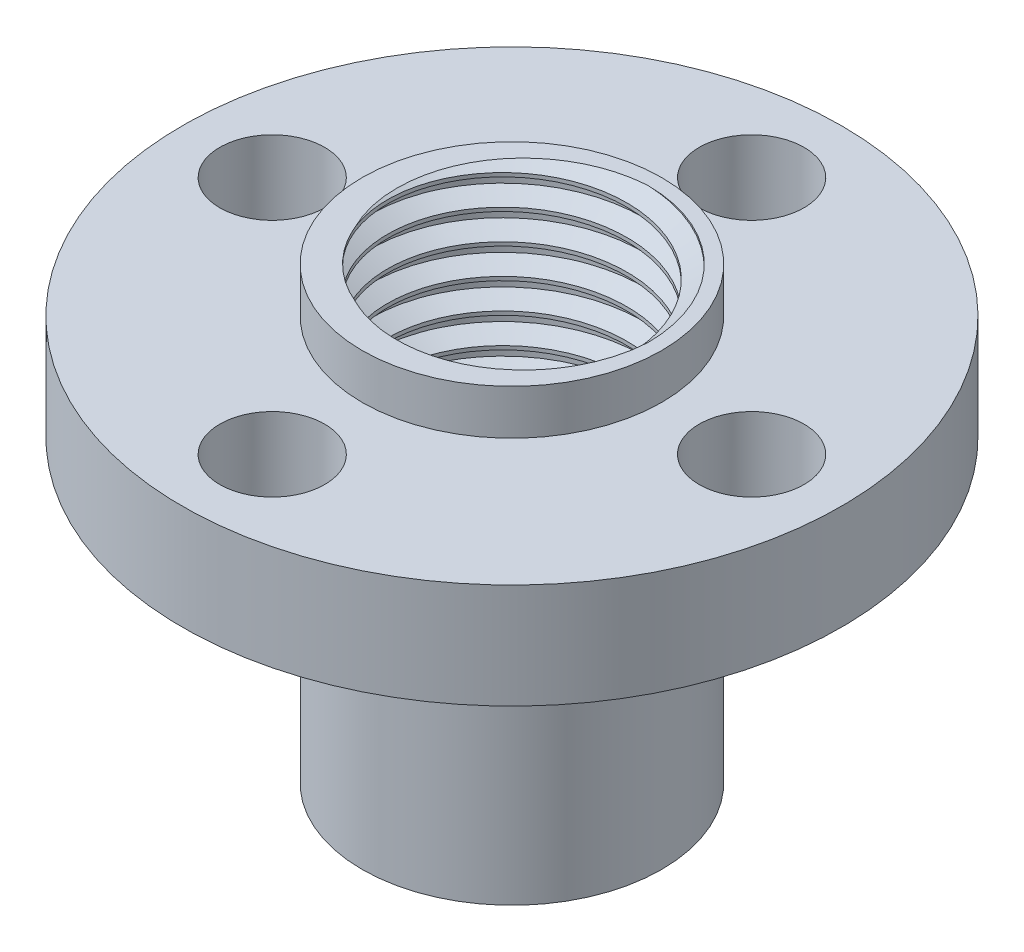
SolidWorks part; units mm, degrees
material "Brass"
ref_plane "Front Plane" through (0, 0, 0) normal (0, 0, 1) x (1, 0, 0)
ref_plane "Top Plane" through (0, 0, 0) normal (0, 1, 0) x (1, 0, 0)
ref_plane "Right Plane" through (0, 0, 0) normal (1, 0, 0) x (0, 0, -1)
sketch "Sketch1" plane through (0, 0, 0) normal (0, 1, 0) x (1, 0, 0)
  circle A0 centre (0, 0) radius 5
  circle A1 centre (0, 0) radius 4.54
  dimension "D1" = 9.08
  dimension "D2" = 10
extrude "Boss-Extrude1" add sketch "Sketch1" along normal blind 1.5
sketch "Sketch11" plane through (0, 0, 0) normal (0, -1, 0) x (1, 0, 0)
  circle A0 centre (0, 0) radius 4.54
  circle A1 centre (0, 0) radius 11
  dimension "D1" = 22
extrude "Boss-Extrude4" add sketch "Sketch11" along normal blind 3.5
sketch "Sketch12" plane through (0, -3.5, 0) normal (0, -1, 0) x (1, 0, 0)
  circle A0 centre (0, 0) radius 4.54
  circle A1 centre (0, 0) radius 5
  dimension "D1" = 10
extrude "Boss-Extrude5" add sketch "Sketch12" along normal blind 10
thread "Thread1" pitch 1 method extrude profile "Thread Profile2" start angle 0, offset 1, length 0, pitch 1, diameter 9.08
ref_plane "Plane2" through (4.54, -14.5, 0) normal (0, 0, 1) x (1, 0, 0)
sketch "Thread Profile2" plane through (4.54, -14.5, 0) normal (0, 0, 1) x (1, 0, 0)
  line L0 (0, 0) -> (0, 1) construction
  line L1 (0, 0.75) -> (-0.5413, 0.4375)
  line L2 (-0.5413, 0.4375) -> (-0.5413, 0.3125)
  line L3 (-0.5413, 0.3125) -> (0, 0)
  line L4 (-0.5413, 0.375) -> (0, 0.375) construction
  line L11 (0, 0.75) -> (0, 0)
  point P6 (0, 0)
  dimension "Pitch" = 1
  dimension "Profile_Angle" = 60
  dimension "Profile_Land" = 0.125
  dimension "Profile_Height" = 0.5413
sketch "Sketch16" plane through (0, 1.5, 0) normal (0, 1, 0) x (1, 0, 0)
  circle A0 centre (0, 0) radius 6.1187
extrude "Cut-Extrude1" cut sketch "Sketch16" along normal blind 4
sketch "Sketch17" plane through (0, -13.5, 0) normal (0, -1, 0) x (1, 0, 0)
  circle A0 centre (0, 0) radius 6.5415
extrude "Cut-Extrude2" cut sketch "Sketch17" along normal blind 5
sketch "Sketch18" plane through (0, 0, 0) normal (0, 1, 0) x (1, 0, 0)
  circle A1 centre (0, 8) radius 1.75
  circle A2 centre (8, 0) radius 1.75
  circle A3 centre (0, -8) radius 1.75
  circle A4 centre (-8, 0) radius 1.75
  point P14 (0, 0)
  dimension "D1" = 8
  dimension "D2" = 3.5
  dimension "D3" = 4
extrude "Cut-Extrude3" cut sketch "Sketch18" against normal blind 5
